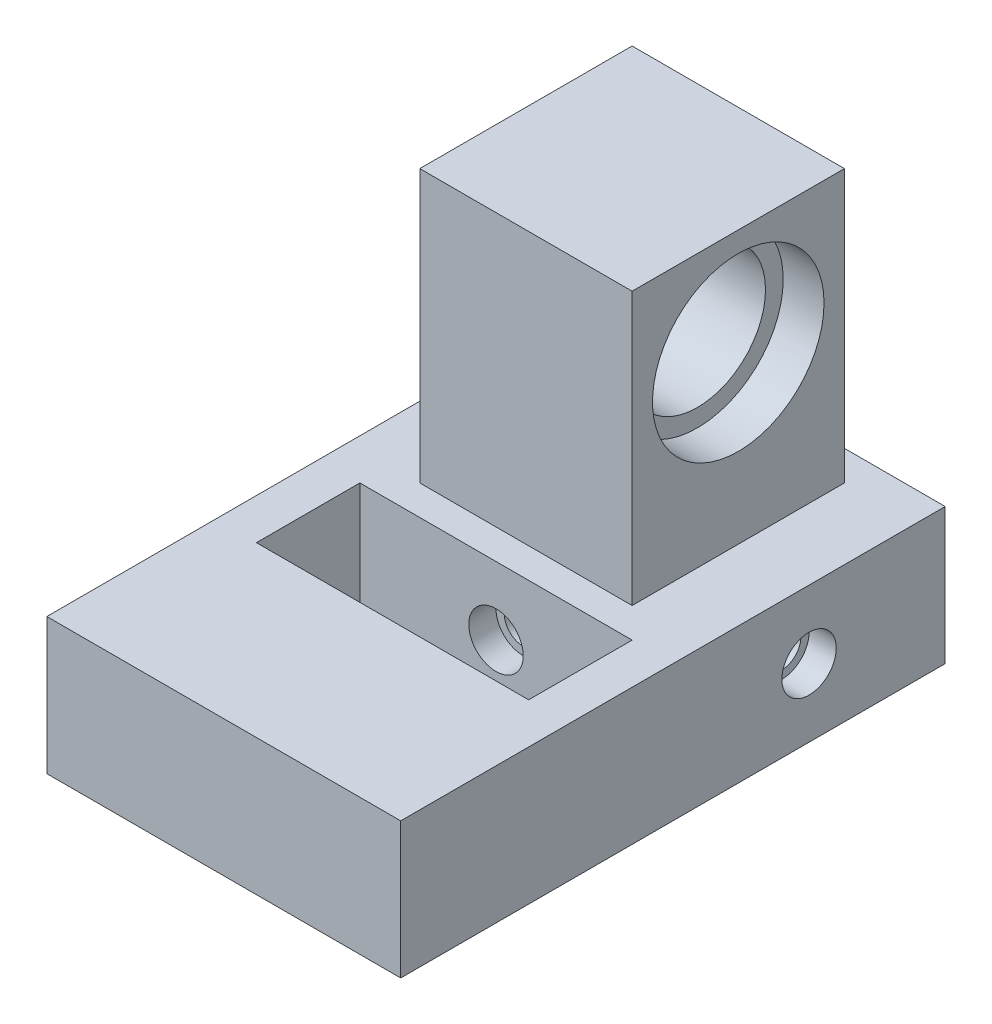
SolidWorks part; units mm, degrees
ref_plane "前视基准面" through (0, 0, 0) normal (0, 0, 1) x (1, 0, 0)
ref_plane "上视基准面" through (0, 0, 0) normal (0, 1, 0) x (1, 0, 0)
ref_plane "右视基准面" through (0, 0, 0) normal (1, 0, 0) x (0, 0, -1)
other "Configuration Table"
sketch "草图1" plane through (0, 0, 0) normal (0, 1, 0) x (1, 0, 0)
  line L1 (-3.1, -3.1) -> (3.1, -3.1)
  line L2 (-3.1, -3.1) -> (-3.1, 3.1)
  line L3 (-3.1, 3.1) -> (3.1, 3.1)
  line L4 (3.1, -3.1) -> (3.1, 3.1)
  line L5 (-3.1, -3.1) -> (3.1, 3.1) construction
  line L6 (-3.1, 3.1) -> (3.1, -3.1) construction
  line L7 (-6.5, -5) -> (6.5, -5)
  line L8 (-6.5, -5) -> (-6.5, 5)
  line L9 (-6.5, 5) -> (6.5, 5)
  line L10 (6.5, -5) -> (6.5, 5)
  line L11 (-6.5, -5) -> (6.5, 5) construction
  line L12 (-6.5, 5) -> (6.5, -5) construction
  circle A0 centre (0, 0) radius 1.25
  dimension "D2" = 2.5
  dimension "D1" = 6.2
  dimension "D3" = 13
  dimension "D4" = 10
extrude "凸台-拉伸1" add sketch "草图1" along normal blind 4 contours L7 L10 L9 L8 L4 L1 L2 L3 | A0 region at (-6.336, 0, 0)
extrude "凸台-拉伸2" add sketch "草图1<3>" along normal blind 1 from surface contours L8 L9 L10 L7 starting at face at (0, 4, 0)
sketch "草图1<3>" plane through (0, 0, 0) normal (0, 1, 0) x (1, 0, 0) same geometry as "草图1"
sketch "草图2" plane through (0, 5, 0) normal (0, 1, 0) x (1, 0, 0)
  line L1 (-3.9, -3.9) -> (3.9, -3.9)
  line L2 (-3.9, -3.9) -> (-3.9, 3.9)
  line L3 (-3.9, 3.9) -> (3.9, 3.9)
  line L4 (3.9, -3.9) -> (3.9, 3.9)
  line L5 (-3.9, -3.9) -> (3.9, 3.9) construction
  line L6 (-3.9, 3.9) -> (3.9, -3.9) construction
  point P0 (0, 0)
  dimension "D1" = 7.8
  dimension "D2" = 7.8
extrude "凸台-拉伸3" add sketch "草图2" along normal blind 10 contours L4 L3 L2 L1
sketch "草图3" plane through (3.9, 0, 0) normal (1, 0, 0) x (0, 0, -1)
  line L0 (-3.9, 15) -> (3.9, 15) construction
  circle A0 centre (0, 11.1) radius 3.15
  circle A1 centre (0, 11.1) radius 2.5
  dimension "D2" = 6.3
  dimension "D3" = 5
  dimension "D1" = 3.9
extrude "切除-拉伸1" cut sketch "草图3" against normal through all contours A1
extrude "切除-拉伸2" cut sketch "草图3<3>" against normal blind 1.5 contours A0 A1 region at (3.9, 11.1, 3.0609)
sketch "草图3<3>" plane through (3.9, 0, 0) normal (1, 0, 0) x (0, 0, -1) same geometry as "草图3"
extrude "切除-拉伸3" cut sketch "草图3<4>" along normal blind 1.5 from surface contours A0 A1 region at (3.9, 11.1, 3.0609) starting at face at (-3.9, 11.1, 2.5)
sketch "草图3<4>" plane through (3.9, 0, 0) normal (1, 0, 0) x (0, 0, -1) same geometry as "草图3"
sketch "草图4" plane through (6.5, 0, 0) normal (1, 0, 0) x (0, 0, -1)
  line L0 (0, 5) -> (0, 0) construction
  line L1 (-3.9, 5) -> (3.9, 5) construction
  circle A0 centre (0, 2.5) radius 1
  circle A1 centre (0, 2.5) radius 0.7
  dimension "D1" = 2
  dimension "D2" = 1.4
extrude "切除-拉伸4" cut sketch "草图4" against normal blind 1
extrude "切除-拉伸5" cut sketch "草图4<2>" along normal blind 1 from surface starting at face at (-6.5, 2.5, 0)
sketch "草图4<2>" plane through (6.5, 0, 0) normal (1, 0, 0) x (0, 0, -1) same geometry as "草图4"
extrude "切除-拉伸6" cut sketch "草图4<3>" against normal up to next contours A1
sketch "草图4<3>" plane through (6.5, 0, 0) normal (1, 0, 0) x (0, 0, -1) same geometry as "草图4"
extrude "切除-拉伸7" cut sketch "草图4<4>" along normal up to next from surface contours A1 starting at face at (-6.5, 2.5, 1)
sketch "草图4<4>" plane through (6.5, 0, 0) normal (1, 0, 0) x (0, 0, -1) same geometry as "草图4"
sketch "草图5" plane through (0, 0, -5) normal (0, 0, -1) x (-1, 0, 0)
  line L0 (0, 5) -> (0, 0) construction
  line L1 (-6.5, 5) -> (6.5, 5) construction
  line L2 (6.5, 0) -> (-6.5, 0) construction
  circle A0 centre (0, 2.5) radius 1
  circle A1 centre (0, 2.5) radius 0.7
  dimension "D1" = 2
  dimension "D2" = 1.4
extrude "切除-拉伸8" cut sketch "草图5" against normal up to next contours A1
extrude "切除-拉伸9" cut sketch "草图5<3>" along normal up to next from surface contours A1 starting at face at (0, 2.5, 5)
sketch "草图5<3>" plane through (0, 0, -5) normal (0, 0, -1) x (-1, 0, 0) same geometry as "草图5"
extrude "切除-拉伸10" cut sketch "草图5<4>" against normal blind 1 contours A0
sketch "草图5<4>" plane through (0, 0, -5) normal (0, 0, -1) x (-1, 0, 0) same geometry as "草图5"
extrude "切除-拉伸11" cut sketch "草图5<5>" along normal blind 1 from surface contours A0 starting at face at (-0.7, 2.5, 5)
sketch "草图5<5>" plane through (0, 0, -5) normal (0, 0, -1) x (-1, 0, 0) same geometry as "草图5"
sketch "草图6" plane through (0, 0, 5) normal (0, 0, 1) x (1, 0, 0)
  line L0 (6.5, 5) -> (-6.5, 5) construction
  line L1 (6.5, 0) -> (5, 0)
  line L2 (6.5, 0) -> (6.5, 5)
  line L3 (6.5, 5) -> (5, 5)
  line L4 (5, 0) -> (5, 5)
  line L5 (-6.5, 0) -> (-5, 0)
  line L6 (-6.5, 0) -> (-6.5, 5)
  line L7 (-6.5, 5) -> (-5, 5)
  line L8 (-5, 0) -> (-5, 5)
  point P10 (0, 0)
  point P11 (0, 0)
  line M7 (-6.5, 0) -> (6.5, 0)
  line M8 (6.5, 0) -> (6.5, 5)
  line M9 (6.5, 5) -> (-6.5, 5)
  line M10 (-6.5, 5) -> (-6.5, 0)
  dimension "D1" = 1.5
extrude "凸台-拉伸4" add sketch "草图6" along normal blind 10 contours L8 M7 M9 M10 | L4 M7 M8 M9 region at (5.75, 2.5, 5) region at (-5.75, 2.5, 5)
sketch "草图7" plane through (5, 0, 0) normal (-1, 0, 0) x (0, 0, 1)
  line L0 (-5, 5) -> (15, 5) construction
  line L1 (15, 0) -> (8.8, 0)
  line L2 (15, 0) -> (15, 5)
  line L3 (15, 5) -> (8.8, 5)
  line L4 (8.8, 0) -> (8.8, 5)
  line M4 (5, 0) -> (15, 0)
  line M5 (15, 0) -> (15, 5)
  line M6 (15, 5) -> (5, 5)
  dimension "D1" = 6.2
extrude "凸台-拉伸5" add sketch "草图7" along normal up to next contours L4 M4 M5 M6 region at (5, 2.5, 11.9)
